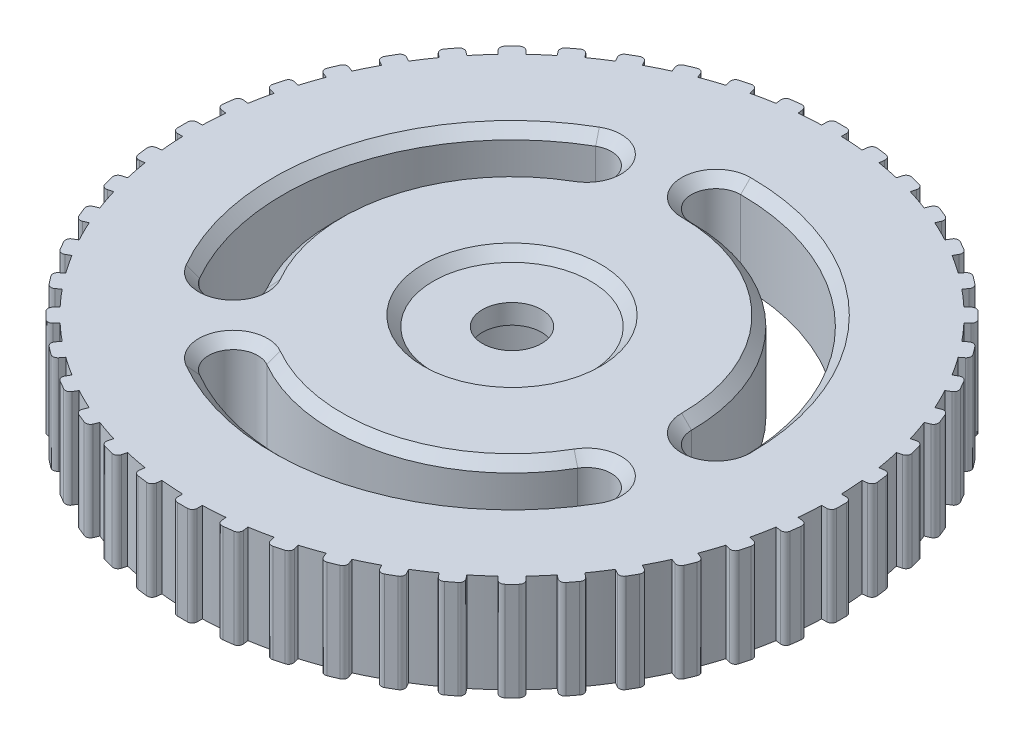
SolidWorks part; units mm, degrees
ref_plane "Front Plane" through (0, 0, 0) normal (0, 0, 1) x (1, 0, 0)
ref_plane "Top Plane" through (0, 0, 0) normal (0, 1, 0) x (1, 0, 0)
ref_plane "Right Plane" through (0, 0, 0) normal (1, 0, 0) x (0, 0, -1)
sketch "Sketch1" plane through (0, 0, 0) normal (0, 1, 0) x (1, 0, 0)
  line L0 (0, 65) -> (2, 65)
  line L1 (0, 65) -> (-2, 65)
  line L2 (-2, 65) -> (-2, 66)
  line L3 (2, 65) -> (2, 66)
  line L4 (-1, 67) -> (1, 67)
  line L5 (7.7538, 66.5573) -> (9.7367, 66.2963)
  line L6 (10.4671, 64.1829) -> (10.5976, 65.1743)
  line L7 (8.4842, 64.4439) -> (10.4671, 64.1829)
  line L8 (8.4842, 64.4439) -> (6.5013, 64.705)
  line L9 (6.5013, 64.705) -> (6.6318, 65.6964)
  line L10 (16.375, 64.9758) -> (18.3068, 64.4582)
  line L11 (18.7551, 62.2675) -> (19.0139, 63.2335)
  line L12 (16.8232, 62.7852) -> (18.7551, 62.2675)
  line L13 (16.8232, 62.7852) -> (14.8914, 63.3028)
  line L14 (14.8914, 63.3028) -> (15.1502, 64.2687)
  line L15 (24.7159, 62.2826) -> (26.5637, 61.5172)
  line L16 (26.7222, 59.2868) -> (27.1049, 60.2107)
  line L17 (24.8744, 60.0522) -> (26.7222, 59.2868)
  line L18 (24.8744, 60.0522) -> (23.0267, 60.8175)
  line L19 (23.0267, 60.8175) -> (23.4093, 61.7414)
  line L20 (32.634, 58.5237) -> (34.366, 57.5237)
  line L21 (34.2321, 55.2917) -> (34.7321, 56.1577)
  line L22 (32.5, 56.2917) -> (34.2321, 55.2917)
  line L23 (32.5, 56.2917) -> (30.7679, 57.2917)
  line L24 (30.7679, 57.2917) -> (31.2679, 58.1577)
  line L25 (39.9937, 53.7634) -> (41.5804, 52.5459)
  line L26 (41.1562, 50.3504) -> (41.765, 51.1438)
  line L27 (39.5695, 51.568) -> (41.1562, 50.3504)
  line L28 (39.5695, 51.568) -> (37.9828, 52.7855)
  line L29 (37.9828, 52.7855) -> (38.5915, 53.5788)
  line L30 (46.669, 48.0833) -> (48.0833, 46.669)
  line L31 (47.3762, 44.5477) -> (48.0833, 45.2548)
  line L32 (45.9619, 45.9619) -> (47.3762, 44.5477)
  line L33 (45.9619, 45.9619) -> (44.5477, 47.3762)
  line L34 (44.5477, 47.3762) -> (45.2548, 48.0833)
  line L35 (52.5459, 41.5804) -> (53.7634, 39.9937)
  line L36 (52.7855, 37.9828) -> (53.5788, 38.5915)
  line L37 (51.568, 39.5695) -> (52.7855, 37.9828)
  line L38 (51.568, 39.5695) -> (50.3504, 41.1562)
  line L39 (50.3504, 41.1562) -> (51.1438, 41.765)
  line L40 (57.5237, 34.366) -> (58.5237, 32.634)
  line L41 (57.2917, 30.7679) -> (58.1577, 31.2679)
  line L42 (56.2917, 32.5) -> (57.2917, 30.7679)
  line L43 (56.2917, 32.5) -> (55.2917, 34.2321)
  line L44 (55.2917, 34.2321) -> (56.1577, 34.7321)
  line L45 (61.5172, 26.5637) -> (62.2826, 24.7159)
  line L46 (60.8175, 23.0267) -> (61.7414, 23.4093)
  line L47 (60.0522, 24.8744) -> (60.8175, 23.0267)
  line L48 (60.0522, 24.8744) -> (59.2868, 26.7222)
  line L49 (59.2868, 26.7222) -> (60.2107, 27.1049)
  line L50 (64.4582, 18.3068) -> (64.9758, 16.375)
  line L51 (63.3028, 14.8914) -> (64.2687, 15.1502)
  line L52 (62.7852, 16.8232) -> (63.3028, 14.8914)
  line L53 (62.7852, 16.8232) -> (62.2675, 18.7551)
  line L54 (62.2675, 18.7551) -> (63.2335, 19.0139)
  line L55 (66.2963, 9.7367) -> (66.5573, 7.7538)
  line L56 (64.705, 6.5013) -> (65.6964, 6.6318)
  line L57 (64.4439, 8.4842) -> (64.705, 6.5013)
  line L58 (64.4439, 8.4842) -> (64.1829, 10.4671)
  line L59 (64.1829, 10.4671) -> (65.1743, 10.5976)
  line L60 (67, 1) -> (67, -1)
  line L61 (65, -2) -> (66, -2)
  line L62 (65, 0) -> (65, -2)
  line L63 (65, 0) -> (65, 2)
  line L64 (65, 2) -> (66, 2)
  line L65 (66.5573, -7.7538) -> (66.2963, -9.7367)
  line L66 (64.1829, -10.4671) -> (65.1743, -10.5976)
  line L67 (64.4439, -8.4842) -> (64.1829, -10.4671)
  line L68 (64.4439, -8.4842) -> (64.705, -6.5013)
  line L69 (64.705, -6.5013) -> (65.6964, -6.6318)
  line L70 (64.9758, -16.375) -> (64.4582, -18.3068)
  line L71 (62.2675, -18.7551) -> (63.2335, -19.0139)
  line L72 (62.7852, -16.8232) -> (62.2675, -18.7551)
  line L73 (62.7852, -16.8232) -> (63.3028, -14.8914)
  line L74 (63.3028, -14.8914) -> (64.2687, -15.1502)
  line L75 (62.2826, -24.7159) -> (61.5172, -26.5637)
  line L76 (59.2868, -26.7222) -> (60.2107, -27.1049)
  line L77 (60.0522, -24.8744) -> (59.2868, -26.7222)
  line L78 (60.0522, -24.8744) -> (60.8175, -23.0267)
  line L79 (60.8175, -23.0267) -> (61.7414, -23.4093)
  line L80 (58.5237, -32.634) -> (57.5237, -34.366)
  line L81 (55.2917, -34.2321) -> (56.1577, -34.7321)
  line L82 (56.2917, -32.5) -> (55.2917, -34.2321)
  line L83 (56.2917, -32.5) -> (57.2917, -30.7679)
  line L84 (57.2917, -30.7679) -> (58.1577, -31.2679)
  line L85 (53.7634, -39.9937) -> (52.5459, -41.5804)
  line L86 (50.3504, -41.1562) -> (51.1438, -41.765)
  line L87 (51.568, -39.5695) -> (50.3504, -41.1562)
  line L88 (51.568, -39.5695) -> (52.7855, -37.9828)
  line L89 (52.7855, -37.9828) -> (53.5788, -38.5915)
  line L90 (48.0833, -46.669) -> (46.669, -48.0833)
  line L91 (44.5477, -47.3762) -> (45.2548, -48.0833)
  line L92 (45.9619, -45.9619) -> (44.5477, -47.3762)
  line L93 (45.9619, -45.9619) -> (47.3762, -44.5477)
  line L94 (47.3762, -44.5477) -> (48.0833, -45.2548)
  line L95 (41.5804, -52.5459) -> (39.9937, -53.7634)
  line L96 (37.9828, -52.7855) -> (38.5915, -53.5788)
  line L97 (39.5695, -51.568) -> (37.9828, -52.7855)
  line L98 (39.5695, -51.568) -> (41.1562, -50.3504)
  line L99 (41.1562, -50.3504) -> (41.765, -51.1438)
  line L100 (34.366, -57.5237) -> (32.634, -58.5237)
  line L101 (30.7679, -57.2917) -> (31.2679, -58.1577)
  line L102 (32.5, -56.2917) -> (30.7679, -57.2917)
  line L103 (32.5, -56.2917) -> (34.2321, -55.2917)
  line L104 (34.2321, -55.2917) -> (34.7321, -56.1577)
  line L105 (26.5637, -61.5172) -> (24.7159, -62.2826)
  line L106 (23.0267, -60.8175) -> (23.4093, -61.7414)
  line L107 (24.8744, -60.0522) -> (23.0267, -60.8175)
  line L108 (24.8744, -60.0522) -> (26.7222, -59.2868)
  line L109 (26.7222, -59.2868) -> (27.1049, -60.2107)
  line L110 (18.3068, -64.4582) -> (16.375, -64.9758)
  line L111 (14.8914, -63.3028) -> (15.1502, -64.2687)
  line L112 (16.8232, -62.7852) -> (14.8914, -63.3028)
  line L113 (16.8232, -62.7852) -> (18.7551, -62.2675)
  line L114 (18.7551, -62.2675) -> (19.0139, -63.2335)
  line L115 (9.7367, -66.2963) -> (7.7538, -66.5573)
  line L116 (6.5013, -64.705) -> (6.6318, -65.6964)
  line L117 (8.4842, -64.4439) -> (6.5013, -64.705)
  line L118 (8.4842, -64.4439) -> (10.4671, -64.1829)
  line L119 (10.4671, -64.1829) -> (10.5976, -65.1743)
  line L120 (1, -67) -> (-1, -67)
  line L121 (-2, -65) -> (-2, -66)
  line L122 (0, -65) -> (-2, -65)
  line L123 (0, -65) -> (2, -65)
  line L124 (2, -65) -> (2, -66)
  line L125 (-7.7538, -66.5573) -> (-9.7367, -66.2963)
  line L126 (-10.4671, -64.1829) -> (-10.5976, -65.1743)
  line L127 (-8.4842, -64.4439) -> (-10.4671, -64.1829)
  line L128 (-8.4842, -64.4439) -> (-6.5013, -64.705)
  line L129 (-6.5013, -64.705) -> (-6.6318, -65.6964)
  line L130 (-16.375, -64.9758) -> (-18.3068, -64.4582)
  line L131 (-18.7551, -62.2675) -> (-19.0139, -63.2335)
  line L132 (-16.8232, -62.7852) -> (-18.7551, -62.2675)
  line L133 (-16.8232, -62.7852) -> (-14.8914, -63.3028)
  line L134 (-14.8914, -63.3028) -> (-15.1502, -64.2687)
  line L135 (-24.7159, -62.2826) -> (-26.5637, -61.5172)
  line L136 (-26.7222, -59.2868) -> (-27.1049, -60.2107)
  line L137 (-24.8744, -60.0522) -> (-26.7222, -59.2868)
  line L138 (-24.8744, -60.0522) -> (-23.0267, -60.8175)
  line L139 (-23.0267, -60.8175) -> (-23.4093, -61.7414)
  line L140 (-32.634, -58.5237) -> (-34.366, -57.5237)
  line L141 (-34.2321, -55.2917) -> (-34.7321, -56.1577)
  line L142 (-32.5, -56.2917) -> (-34.2321, -55.2917)
  line L143 (-32.5, -56.2917) -> (-30.7679, -57.2917)
  line L144 (-30.7679, -57.2917) -> (-31.2679, -58.1577)
  line L145 (-39.9937, -53.7634) -> (-41.5804, -52.5459)
  line L146 (-41.1562, -50.3504) -> (-41.765, -51.1438)
  line L147 (-39.5695, -51.568) -> (-41.1562, -50.3504)
  line L148 (-39.5695, -51.568) -> (-37.9828, -52.7855)
  line L149 (-37.9828, -52.7855) -> (-38.5915, -53.5788)
  line L150 (-46.669, -48.0833) -> (-48.0833, -46.669)
  line L151 (-47.3762, -44.5477) -> (-48.0833, -45.2548)
  line L152 (-45.9619, -45.9619) -> (-47.3762, -44.5477)
  line L153 (-45.9619, -45.9619) -> (-44.5477, -47.3762)
  line L154 (-44.5477, -47.3762) -> (-45.2548, -48.0833)
  line L155 (-52.5459, -41.5804) -> (-53.7634, -39.9937)
  line L156 (-52.7855, -37.9828) -> (-53.5788, -38.5915)
  line L157 (-51.568, -39.5695) -> (-52.7855, -37.9828)
  line L158 (-51.568, -39.5695) -> (-50.3504, -41.1562)
  line L159 (-50.3504, -41.1562) -> (-51.1438, -41.765)
  line L160 (-57.5237, -34.366) -> (-58.5237, -32.634)
  line L161 (-57.2917, -30.7679) -> (-58.1577, -31.2679)
  line L162 (-56.2917, -32.5) -> (-57.2917, -30.7679)
  line L163 (-56.2917, -32.5) -> (-55.2917, -34.2321)
  line L164 (-55.2917, -34.2321) -> (-56.1577, -34.7321)
  line L165 (-61.5172, -26.5637) -> (-62.2826, -24.7159)
  line L166 (-60.8175, -23.0267) -> (-61.7414, -23.4093)
  line L167 (-60.0522, -24.8744) -> (-60.8175, -23.0267)
  line L168 (-60.0522, -24.8744) -> (-59.2868, -26.7222)
  line L169 (-59.2868, -26.7222) -> (-60.2107, -27.1049)
  line L170 (-64.4582, -18.3068) -> (-64.9758, -16.375)
  line L171 (-63.3028, -14.8914) -> (-64.2687, -15.1502)
  line L172 (-62.7852, -16.8232) -> (-63.3028, -14.8914)
  line L173 (-62.7852, -16.8232) -> (-62.2675, -18.7551)
  line L174 (-62.2675, -18.7551) -> (-63.2335, -19.0139)
  line L175 (-66.2963, -9.7367) -> (-66.5573, -7.7538)
  line L176 (-64.705, -6.5013) -> (-65.6964, -6.6318)
  line L177 (-64.4439, -8.4842) -> (-64.705, -6.5013)
  line L178 (-64.4439, -8.4842) -> (-64.1829, -10.4671)
  line L179 (-64.1829, -10.4671) -> (-65.1743, -10.5976)
  line L180 (-67, -1) -> (-67, 1)
  line L181 (-65, 2) -> (-66, 2)
  line L182 (-65, 0) -> (-65, 2)
  line L183 (-65, 0) -> (-65, -2)
  line L184 (-65, -2) -> (-66, -2)
  line L185 (-66.5573, 7.7538) -> (-66.2963, 9.7367)
  line L186 (-64.1829, 10.4671) -> (-65.1743, 10.5976)
  line L187 (-64.4439, 8.4842) -> (-64.1829, 10.4671)
  line L188 (-64.4439, 8.4842) -> (-64.705, 6.5013)
  line L189 (-64.705, 6.5013) -> (-65.6964, 6.6318)
  line L190 (-64.9758, 16.375) -> (-64.4582, 18.3068)
  line L191 (-62.2675, 18.7551) -> (-63.2335, 19.0139)
  line L192 (-62.7852, 16.8232) -> (-62.2675, 18.7551)
  line L193 (-62.7852, 16.8232) -> (-63.3028, 14.8914)
  line L194 (-63.3028, 14.8914) -> (-64.2687, 15.1502)
  line L195 (-62.2826, 24.7159) -> (-61.5172, 26.5637)
  line L196 (-59.2868, 26.7222) -> (-60.2107, 27.1049)
  line L197 (-60.0522, 24.8744) -> (-59.2868, 26.7222)
  line L198 (-60.0522, 24.8744) -> (-60.8175, 23.0267)
  line L199 (-60.8175, 23.0267) -> (-61.7414, 23.4093)
  line L200 (-58.5237, 32.634) -> (-57.5237, 34.366)
  line L201 (-55.2917, 34.2321) -> (-56.1577, 34.7321)
  line L202 (-56.2917, 32.5) -> (-55.2917, 34.2321)
  line L203 (-56.2917, 32.5) -> (-57.2917, 30.7679)
  line L204 (-57.2917, 30.7679) -> (-58.1577, 31.2679)
  line L205 (-53.7634, 39.9937) -> (-52.5459, 41.5804)
  line L206 (-50.3504, 41.1562) -> (-51.1438, 41.765)
  line L207 (-51.568, 39.5695) -> (-50.3504, 41.1562)
  line L208 (-51.568, 39.5695) -> (-52.7855, 37.9828)
  line L209 (-52.7855, 37.9828) -> (-53.5788, 38.5915)
  line L210 (-48.0833, 46.669) -> (-46.669, 48.0833)
  line L211 (-44.5477, 47.3762) -> (-45.2548, 48.0833)
  line L212 (-45.9619, 45.9619) -> (-44.5477, 47.3762)
  line L213 (-45.9619, 45.9619) -> (-47.3762, 44.5477)
  line L214 (-47.3762, 44.5477) -> (-48.0833, 45.2548)
  line L215 (-41.5804, 52.5459) -> (-39.9937, 53.7634)
  line L216 (-37.9828, 52.7855) -> (-38.5915, 53.5788)
  line L217 (-39.5695, 51.568) -> (-37.9828, 52.7855)
  line L218 (-39.5695, 51.568) -> (-41.1562, 50.3504)
  line L219 (-41.1562, 50.3504) -> (-41.765, 51.1438)
  line L220 (-34.366, 57.5237) -> (-32.634, 58.5237)
  line L221 (-30.7679, 57.2917) -> (-31.2679, 58.1577)
  line L222 (-32.5, 56.2917) -> (-30.7679, 57.2917)
  line L223 (-32.5, 56.2917) -> (-34.2321, 55.2917)
  line L224 (-34.2321, 55.2917) -> (-34.7321, 56.1577)
  line L225 (-26.5637, 61.5172) -> (-24.7159, 62.2826)
  line L226 (-23.0267, 60.8175) -> (-23.4093, 61.7414)
  line L227 (-24.8744, 60.0522) -> (-23.0267, 60.8175)
  line L228 (-24.8744, 60.0522) -> (-26.7222, 59.2868)
  line L229 (-26.7222, 59.2868) -> (-27.1049, 60.2107)
  line L230 (-18.3068, 64.4582) -> (-16.375, 64.9758)
  line L231 (-14.8914, 63.3028) -> (-15.1502, 64.2687)
  line L232 (-16.8232, 62.7852) -> (-14.8914, 63.3028)
  line L233 (-16.8232, 62.7852) -> (-18.7551, 62.2675)
  line L234 (-18.7551, 62.2675) -> (-19.0139, 63.2335)
  line L235 (-9.7367, 66.2963) -> (-7.7538, 66.5573)
  line L236 (-6.5013, 64.705) -> (-6.6318, 65.6964)
  line L237 (-8.4842, 64.4439) -> (-6.5013, 64.705)
  line L238 (-8.4842, 64.4439) -> (-10.4671, 64.1829)
  line L239 (-10.4671, 64.1829) -> (-10.5976, 65.1743)
  circle A0 centre (0, 0) radius 18.5
  circle A1 centre (0, 0) radius 65
  arc A2 (-2, 66) -> (-1, 67) centre (-1, 66) cw
  arc A3 (1, 67) -> (2, 66) centre (1, 66) cw
  arc A4 (9.7367, 66.2963) -> (10.5976, 65.1743) centre (9.6062, 65.3048) cw
  arc A5 (6.6318, 65.6964) -> (7.7538, 66.5573) centre (7.6233, 65.5659) cw
  arc A6 (18.3068, 64.4582) -> (19.0139, 63.2335) centre (18.048, 63.4923) cw
  arc A7 (15.1502, 64.2687) -> (16.375, 64.9758) centre (16.1161, 64.0099) cw
  arc A8 (26.5637, 61.5172) -> (27.1049, 60.2107) centre (26.181, 60.5934) cw
  arc A9 (23.4093, 61.7414) -> (24.7159, 62.2826) centre (24.3332, 61.3587) cw
  arc A10 (34.366, 57.5237) -> (34.7321, 56.1577) centre (33.866, 56.6577) cw
  arc A11 (31.2679, 58.1577) -> (32.634, 58.5237) centre (32.134, 57.6577) cw
  arc A12 (41.5804, 52.5459) -> (41.765, 51.1438) centre (40.9716, 51.7526) cw
  arc A13 (38.5915, 53.5788) -> (39.9937, 53.7634) centre (39.3849, 52.9701) cw
  arc A14 (48.0833, 46.669) -> (48.0833, 45.2548) centre (47.3762, 45.9619) cw
  arc A15 (45.2548, 48.0833) -> (46.669, 48.0833) centre (45.9619, 47.3762) cw
  arc A16 (53.7634, 39.9937) -> (53.5788, 38.5915) centre (52.9701, 39.3849) cw
  arc A17 (51.1438, 41.765) -> (52.5459, 41.5804) centre (51.7526, 40.9716) cw
  arc A18 (58.5237, 32.634) -> (58.1577, 31.2679) centre (57.6577, 32.134) cw
  arc A19 (56.1577, 34.7321) -> (57.5237, 34.366) centre (56.6577, 33.866) cw
  arc A20 (62.2826, 24.7159) -> (61.7414, 23.4093) centre (61.3587, 24.3332) cw
  arc A21 (60.2107, 27.1049) -> (61.5172, 26.5637) centre (60.5934, 26.181) cw
  arc A22 (64.9758, 16.375) -> (64.2687, 15.1502) centre (64.0099, 16.1161) cw
  arc A23 (63.2335, 19.0139) -> (64.4582, 18.3068) centre (63.4923, 18.048) cw
  arc A24 (66.5573, 7.7538) -> (65.6964, 6.6318) centre (65.5659, 7.6233) cw
  arc A25 (65.1743, 10.5976) -> (66.2963, 9.7367) centre (65.3048, 9.6062) cw
  arc A26 (67, -1) -> (66, -2) centre (66, -1) cw
  arc A27 (66, 2) -> (67, 1) centre (66, 1) cw
  arc A28 (66.2963, -9.7367) -> (65.1743, -10.5976) centre (65.3048, -9.6062) cw
  arc A29 (65.6964, -6.6318) -> (66.5573, -7.7538) centre (65.5659, -7.6233) cw
  arc A30 (64.4582, -18.3068) -> (63.2335, -19.0139) centre (63.4923, -18.048) cw
  arc A31 (64.2687, -15.1502) -> (64.9758, -16.375) centre (64.0099, -16.1161) cw
  arc A32 (61.5172, -26.5637) -> (60.2107, -27.1049) centre (60.5934, -26.181) cw
  arc A33 (61.7414, -23.4093) -> (62.2826, -24.7159) centre (61.3587, -24.3332) cw
  arc A34 (57.5237, -34.366) -> (56.1577, -34.7321) centre (56.6577, -33.866) cw
  arc A35 (58.1577, -31.2679) -> (58.5237, -32.634) centre (57.6577, -32.134) cw
  arc A36 (52.5459, -41.5804) -> (51.1438, -41.765) centre (51.7526, -40.9716) cw
  arc A37 (53.5788, -38.5915) -> (53.7634, -39.9937) centre (52.9701, -39.3849) cw
  arc A38 (46.669, -48.0833) -> (45.2548, -48.0833) centre (45.9619, -47.3762) cw
  arc A39 (48.0833, -45.2548) -> (48.0833, -46.669) centre (47.3762, -45.9619) cw
  arc A40 (39.9937, -53.7634) -> (38.5915, -53.5788) centre (39.3849, -52.9701) cw
  arc A41 (41.765, -51.1438) -> (41.5804, -52.5459) centre (40.9716, -51.7526) cw
  arc A42 (32.634, -58.5237) -> (31.2679, -58.1577) centre (32.134, -57.6577) cw
  arc A43 (34.7321, -56.1577) -> (34.366, -57.5237) centre (33.866, -56.6577) cw
  arc A44 (24.7159, -62.2826) -> (23.4093, -61.7414) centre (24.3332, -61.3587) cw
  arc A45 (27.1049, -60.2107) -> (26.5637, -61.5172) centre (26.181, -60.5934) cw
  arc A46 (16.375, -64.9758) -> (15.1502, -64.2687) centre (16.1161, -64.0099) cw
  arc A47 (19.0139, -63.2335) -> (18.3068, -64.4582) centre (18.048, -63.4923) cw
  arc A48 (7.7538, -66.5573) -> (6.6318, -65.6964) centre (7.6233, -65.5659) cw
  arc A49 (10.5976, -65.1743) -> (9.7367, -66.2963) centre (9.6062, -65.3048) cw
  arc A50 (-1, -67) -> (-2, -66) centre (-1, -66) cw
  arc A51 (2, -66) -> (1, -67) centre (1, -66) cw
  arc A52 (-9.7367, -66.2963) -> (-10.5976, -65.1743) centre (-9.6062, -65.3048) cw
  arc A53 (-6.6318, -65.6964) -> (-7.7538, -66.5573) centre (-7.6233, -65.5659) cw
  arc A54 (-18.3068, -64.4582) -> (-19.0139, -63.2335) centre (-18.048, -63.4923) cw
  arc A55 (-15.1502, -64.2687) -> (-16.375, -64.9758) centre (-16.1161, -64.0099) cw
  arc A56 (-26.5637, -61.5172) -> (-27.1049, -60.2107) centre (-26.181, -60.5934) cw
  arc A57 (-23.4093, -61.7414) -> (-24.7159, -62.2826) centre (-24.3332, -61.3587) cw
  arc A58 (-34.366, -57.5237) -> (-34.7321, -56.1577) centre (-33.866, -56.6577) cw
  arc A59 (-31.2679, -58.1577) -> (-32.634, -58.5237) centre (-32.134, -57.6577) cw
  arc A60 (-41.5804, -52.5459) -> (-41.765, -51.1438) centre (-40.9716, -51.7526) cw
  arc A61 (-38.5915, -53.5788) -> (-39.9937, -53.7634) centre (-39.3849, -52.9701) cw
  arc A62 (-48.0833, -46.669) -> (-48.0833, -45.2548) centre (-47.3762, -45.9619) cw
  arc A63 (-45.2548, -48.0833) -> (-46.669, -48.0833) centre (-45.9619, -47.3762) cw
  arc A64 (-53.7634, -39.9937) -> (-53.5788, -38.5915) centre (-52.9701, -39.3849) cw
  arc A65 (-51.1438, -41.765) -> (-52.5459, -41.5804) centre (-51.7526, -40.9716) cw
  arc A66 (-58.5237, -32.634) -> (-58.1577, -31.2679) centre (-57.6577, -32.134) cw
  arc A67 (-56.1577, -34.7321) -> (-57.5237, -34.366) centre (-56.6577, -33.866) cw
  arc A68 (-62.2826, -24.7159) -> (-61.7414, -23.4093) centre (-61.3587, -24.3332) cw
  arc A69 (-60.2107, -27.1049) -> (-61.5172, -26.5637) centre (-60.5934, -26.181) cw
  arc A70 (-64.9758, -16.375) -> (-64.2687, -15.1502) centre (-64.0099, -16.1161) cw
  arc A71 (-63.2335, -19.0139) -> (-64.4582, -18.3068) centre (-63.4923, -18.048) cw
  arc A72 (-66.5573, -7.7538) -> (-65.6964, -6.6318) centre (-65.5659, -7.6233) cw
  arc A73 (-65.1743, -10.5976) -> (-66.2963, -9.7367) centre (-65.3048, -9.6062) cw
  arc A74 (-67, 1) -> (-66, 2) centre (-66, 1) cw
  arc A75 (-66, -2) -> (-67, -1) centre (-66, -1) cw
  arc A76 (-66.2963, 9.7367) -> (-65.1743, 10.5976) centre (-65.3048, 9.6062) cw
  arc A77 (-65.6964, 6.6318) -> (-66.5573, 7.7538) centre (-65.5659, 7.6233) cw
  arc A78 (-64.4582, 18.3068) -> (-63.2335, 19.0139) centre (-63.4923, 18.048) cw
  arc A79 (-64.2687, 15.1502) -> (-64.9758, 16.375) centre (-64.0099, 16.1161) cw
  arc A80 (-61.5172, 26.5637) -> (-60.2107, 27.1049) centre (-60.5934, 26.181) cw
  arc A81 (-61.7414, 23.4093) -> (-62.2826, 24.7159) centre (-61.3587, 24.3332) cw
  arc A82 (-57.5237, 34.366) -> (-56.1577, 34.7321) centre (-56.6577, 33.866) cw
  arc A83 (-58.1577, 31.2679) -> (-58.5237, 32.634) centre (-57.6577, 32.134) cw
  arc A84 (-52.5459, 41.5804) -> (-51.1438, 41.765) centre (-51.7526, 40.9716) cw
  arc A85 (-53.5788, 38.5915) -> (-53.7634, 39.9937) centre (-52.9701, 39.3849) cw
  arc A86 (-46.669, 48.0833) -> (-45.2548, 48.0833) centre (-45.9619, 47.3762) cw
  arc A87 (-48.0833, 45.2548) -> (-48.0833, 46.669) centre (-47.3762, 45.9619) cw
  arc A88 (-39.9937, 53.7634) -> (-38.5915, 53.5788) centre (-39.3849, 52.9701) cw
  arc A89 (-41.765, 51.1438) -> (-41.5804, 52.5459) centre (-40.9716, 51.7526) cw
  arc A90 (-32.634, 58.5237) -> (-31.2679, 58.1577) centre (-32.134, 57.6577) cw
  arc A91 (-34.7321, 56.1577) -> (-34.366, 57.5237) centre (-33.866, 56.6577) cw
  arc A92 (-24.7159, 62.2826) -> (-23.4093, 61.7414) centre (-24.3332, 61.3587) cw
  arc A93 (-27.1049, 60.2107) -> (-26.5637, 61.5172) centre (-26.181, 60.5934) cw
  arc A94 (-16.375, 64.9758) -> (-15.1502, 64.2687) centre (-16.1161, 64.0099) cw
  arc A95 (-19.0139, 63.2335) -> (-18.3068, 64.4582) centre (-18.048, 63.4923) cw
  arc A96 (-7.7538, 66.5573) -> (-6.6318, 65.6964) centre (-7.6233, 65.5659) cw
  arc A97 (-10.5976, 65.1743) -> (-9.7367, 66.2963) centre (-9.6062, 65.3048) cw
  point P11 (-2, 67)
  point P14 (2, 67)
  point P441 (0, 0)
  dimension "D1" = 130
  dimension "D2" = 37
  dimension "D7" = 1
  dimension "D8" = 1
  dimension "D3" = 2
  dimension "D4" = 2
  dimension "D5" = 2
  dimension "D6" = 2
  dimension "D9" = 48
extrude "Boss-Extrude1" add sketch "Sketch1" along normal blind 20 contours A1 A0 | A59 L144 L143 L142 L141 A58 L140 | A61 L149 L148 L147 L146 A60 L145 | A57 L139 L138 L137 L136 A56 L135 | A55 L134 L133 L132 L131 A54 L130 | A53 L129 L128 L127 L126 A52 L125 | A51 L124 L123 L122 L121 A50 L120 | A49 L119 L118 L117 L116 A48 L115 | A45 L109 L108 L107 L106 A44 L105 | A43 L104 L103 L102 L101 A42 L100 | A41 L99 L98 L97 L96 A40 L95 | A39 L94 L93 L92 L91 A38 L90 | A37 L89 L88 L87 L86 A36 L85 | A35 L84 L83 L82 L81 A34 L80 | A33 L79 L78 L77 L76 A32 L75 | A31 L74 L73 L72 L71 A30 L70 | A29 L69 L68 L67 L66 A28 L65 | A27 L64 L63 L62 L61 A26 L60 | A25 L59 L58 L57 L56 A24 L55 | A21 L49 L48 L47 L46 A20 L45 | A19 L44 L43 L42 L41 A18 L40 | A17 L39 L38 L37 L36 A16 L35 | A15 L34 L33 L32 L31 A14 L30 | A13 L29 L28 L27 L26 A12 L25 | A11 L24 L23 L22 L21 A10 L20 | A9 L19 L18 L17 L16 A8 L15 | A7 L14 L13 L12 L11 A6 L10 | A5 L9 L8 L7 L6 A4 L5 | A3 L4 A2 L2 L1 L0 L3 | A97 L239 L238 L237 L236 A96 L235 | A95 L234 L233 L232 L231 A94 L230 | A89 L219 L218 L217 L216 A88 L215 | A91 L224 L223 L222 L221 A90 L220 | A93 L229 L228 L227 L226 A92 L225 | A85 L209 L208 L207 L206 A84 L205 | A87 L214 L213 L212 L211 A86 L210 | A83 L204 L203 L202 L201 A82 L200 | A77 L189 L188 L187 L186 A76 L185 | A75 L184 L183 L182 L181 A74 L180 | A73 L179 L178 L177 L176 A72 L175 | A71 L174 L173 L172 L171 A70 L170 | A69 L169 L168 L167 L166 A68 L165 | A67 L164 L163 L162 L161 A66 L160 | A65 L159 L158 L157 L156 A64 L155 | A63 L154 L153 L152 L151 A62 L150 | L112 L111 A46 L110 A47 L114 L113 | L52 L51 A22 L50 A23 L54 L53 | L195 A80 L196 L197 L198 L199 A81 | L193 L194 A79 L190 A78 L191 L192 | L177 L176 A72 L175 A73 L179 L178 | L172 L171 A70 L170 A71 L174 L173 region at (0, 0, -65.956) region at (8.609, 0, -65.3917) region at (17.0707, 0, -63.7086) region at (25.2403, 0, -60.9354) region at (32.978, 0, -57.1195) region at (40.1515, 0, -52.3264) region at (46.6379, 0, -46.6379) region at (52.3264, 0, -40.1515) region at (57.1195, 0, -32.978) region at (60.9354, 0, -25.2403) region at (65.3917, 0, -8.609) region at (65.956, 0, 0) region at (65.3917, 0, 8.609) region at (63.7086, 0, 17.0707) region at (60.9354, 0, 25.2403) region at (57.1195, 0, 32.978) region at (52.3264, 0, 40.1515) region at (46.6379, 0, 46.6379) region at (40.1515, 0, 52.3264) region at (32.978, 0, 57.1195) region at (25.2403, 0, 60.9354) region at (8.609, 0, 65.3917) region at (0, 0, 65.956) region at (-8.609, 0, 65.3917) region at (-17.0707, 0, 63.7086) region at (-25.2403, 0, 60.9354) region at (-32.978, 0, 57.1195) region at (-40.1515, 0, 52.3264) region at (-46.6379, 0, 46.6379) region at (-52.3264, 0, 40.1515) region at (-57.1195, 0, 32.978) region at (-60.9354, 0, 25.2403) region at (-63.7086, 0, 17.0707) region at (-65.3917, 0, 8.609) region at (-65.956, 0, 0) region at (-65.3917, 0, -8.609) region at (-57.1195, 0, -32.978) region at (-52.3264, 0, -40.1515) region at (-46.6379, 0, -46.6379) region at (-40.1515, 0, -52.3264) region at (-32.978, 0, -57.1195) region at (-25.2403, 0, -60.9354) region at (-17.0707, 0, -63.7086) region at (-8.609, 0, -65.3917) region at (4.131, 0, -63.0263)
sketch "Sketch2" plane through (0, 20, 0) normal (0, 1, 0) x (1, 0, 0)
  line L0 (6.5013, 64.705) -> (6.2538, 62.8251)
  line L1 (-2, 65) -> (2, 65)
  line L2 (-2, 65) -> (-2, 63.1039)
  line L3 (-2, 63.1039) -> (2, 63.1039)
  line L4 (2, 65) -> (2, 63.1039)
  line L5 (6.5013, 64.705) -> (10.4671, 64.1829)
  line L6 (10.4671, 64.1829) -> (10.2196, 62.303)
  line L7 (6.2538, 62.8251) -> (10.2196, 62.303)
  line L8 (14.8914, 63.3028) -> (14.4006, 61.4713)
  line L9 (14.8914, 63.3028) -> (18.7551, 62.2675)
  line L10 (18.7551, 62.2675) -> (18.2643, 60.4361)
  line L11 (14.4006, 61.4713) -> (18.2643, 60.4361)
  line L12 (23.0267, 60.8175) -> (22.3011, 59.0658)
  line L13 (23.0267, 60.8175) -> (26.7222, 59.2868)
  line L14 (26.7222, 59.2868) -> (25.9966, 57.535)
  line L15 (22.3011, 59.0658) -> (25.9966, 57.535)
  line L16 (30.7679, 57.2917) -> (29.8199, 55.6496)
  line L17 (30.7679, 57.2917) -> (34.2321, 55.2917)
  line L18 (34.2321, 55.2917) -> (33.284, 53.6496)
  line L19 (29.8199, 55.6496) -> (33.284, 53.6496)
  line L20 (37.9828, 52.7855) -> (36.8285, 51.2812)
  line L21 (37.9828, 52.7855) -> (41.1562, 50.3504)
  line L22 (41.1562, 50.3504) -> (40.0019, 48.8462)
  line L23 (36.8285, 51.2812) -> (40.0019, 48.8462)
  line L24 (44.5477, 47.3762) -> (43.207, 46.0354)
  line L25 (44.5477, 47.3762) -> (47.3762, 44.5477)
  line L26 (47.3762, 44.5477) -> (46.0354, 43.207)
  line L27 (43.207, 46.0354) -> (46.0354, 43.207)
  line L28 (50.3504, 41.1562) -> (48.8462, 40.0019)
  line L29 (50.3504, 41.1562) -> (52.7855, 37.9828)
  line L30 (52.7855, 37.9828) -> (51.2812, 36.8285)
  line L31 (48.8462, 40.0019) -> (51.2812, 36.8285)
  line L32 (55.2917, 34.2321) -> (53.6496, 33.284)
  line L33 (55.2917, 34.2321) -> (57.2917, 30.7679)
  line L34 (57.2917, 30.7679) -> (55.6496, 29.8199)
  line L35 (53.6496, 33.284) -> (55.6496, 29.8199)
  line L36 (59.2868, 26.7222) -> (57.535, 25.9966)
  line L37 (59.2868, 26.7222) -> (60.8175, 23.0267)
  line L38 (60.8175, 23.0267) -> (59.0658, 22.3011)
  line L39 (57.535, 25.9966) -> (59.0658, 22.3011)
  line L40 (62.2675, 18.7551) -> (60.4361, 18.2643)
  line L41 (62.2675, 18.7551) -> (63.3028, 14.8914)
  line L42 (63.3028, 14.8914) -> (61.4713, 14.4006)
  line L43 (60.4361, 18.2643) -> (61.4713, 14.4006)
  line L44 (64.1829, 10.4671) -> (62.303, 10.2196)
  line L45 (64.1829, 10.4671) -> (64.705, 6.5013)
  line L46 (64.705, 6.5013) -> (62.8251, 6.2538)
  line L47 (62.303, 10.2196) -> (62.8251, 6.2538)
  line L48 (65, 2) -> (63.1039, 2)
  line L49 (65, 2) -> (65, -2)
  line L50 (65, -2) -> (63.1039, -2)
  line L51 (63.1039, 2) -> (63.1039, -2)
  line L52 (64.705, -6.5013) -> (62.8251, -6.2538)
  line L53 (64.705, -6.5013) -> (64.1829, -10.4671)
  line L54 (64.1829, -10.4671) -> (62.303, -10.2196)
  line L55 (62.8251, -6.2538) -> (62.303, -10.2196)
  line L56 (63.3028, -14.8914) -> (61.4713, -14.4006)
  line L57 (63.3028, -14.8914) -> (62.2675, -18.7551)
  line L58 (62.2675, -18.7551) -> (60.4361, -18.2643)
  line L59 (61.4713, -14.4006) -> (60.4361, -18.2643)
  line L60 (60.8175, -23.0267) -> (59.0658, -22.3011)
  line L61 (60.8175, -23.0267) -> (59.2868, -26.7222)
  line L62 (59.2868, -26.7222) -> (57.535, -25.9966)
  line L63 (59.0658, -22.3011) -> (57.535, -25.9966)
  line L64 (57.2917, -30.7679) -> (55.6496, -29.8199)
  line L65 (57.2917, -30.7679) -> (55.2917, -34.2321)
  line L66 (55.2917, -34.2321) -> (53.6496, -33.284)
  line L67 (55.6496, -29.8199) -> (53.6496, -33.284)
  line L68 (52.7855, -37.9828) -> (51.2812, -36.8285)
  line L69 (52.7855, -37.9828) -> (50.3504, -41.1562)
  line L70 (50.3504, -41.1562) -> (48.8462, -40.0019)
  line L71 (51.2812, -36.8285) -> (48.8462, -40.0019)
  line L72 (47.3762, -44.5477) -> (46.0354, -43.207)
  line L73 (47.3762, -44.5477) -> (44.5477, -47.3762)
  line L74 (44.5477, -47.3762) -> (43.207, -46.0354)
  line L75 (46.0354, -43.207) -> (43.207, -46.0354)
  line L76 (41.1562, -50.3504) -> (40.0019, -48.8462)
  line L77 (41.1562, -50.3504) -> (37.9828, -52.7855)
  line L78 (37.9828, -52.7855) -> (36.8285, -51.2812)
  line L79 (40.0019, -48.8462) -> (36.8285, -51.2812)
  line L80 (34.2321, -55.2917) -> (33.284, -53.6496)
  line L81 (34.2321, -55.2917) -> (30.7679, -57.2917)
  line L82 (30.7679, -57.2917) -> (29.8199, -55.6496)
  line L83 (33.284, -53.6496) -> (29.8199, -55.6496)
  line L84 (26.7222, -59.2868) -> (25.9966, -57.535)
  line L85 (26.7222, -59.2868) -> (23.0267, -60.8175)
  line L86 (23.0267, -60.8175) -> (22.3011, -59.0658)
  line L87 (25.9966, -57.535) -> (22.3011, -59.0658)
  line L88 (18.7551, -62.2675) -> (18.2643, -60.4361)
  line L89 (18.7551, -62.2675) -> (14.8914, -63.3028)
  line L90 (14.8914, -63.3028) -> (14.4006, -61.4713)
  line L91 (18.2643, -60.4361) -> (14.4006, -61.4713)
  line L92 (10.4671, -64.1829) -> (10.2196, -62.303)
  line L93 (10.4671, -64.1829) -> (6.5013, -64.705)
  line L94 (6.5013, -64.705) -> (6.2538, -62.8251)
  line L95 (10.2196, -62.303) -> (6.2538, -62.8251)
  line L96 (2, -65) -> (2, -63.1039)
  line L97 (2, -65) -> (-2, -65)
  line L98 (-2, -65) -> (-2, -63.1039)
  line L99 (2, -63.1039) -> (-2, -63.1039)
  line L100 (-6.5013, -64.705) -> (-6.2538, -62.8251)
  line L101 (-6.5013, -64.705) -> (-10.4671, -64.1829)
  line L102 (-10.4671, -64.1829) -> (-10.2196, -62.303)
  line L103 (-6.2538, -62.8251) -> (-10.2196, -62.303)
  line L104 (-14.8914, -63.3028) -> (-14.4006, -61.4713)
  line L105 (-14.8914, -63.3028) -> (-18.7551, -62.2675)
  line L106 (-18.7551, -62.2675) -> (-18.2643, -60.4361)
  line L107 (-14.4006, -61.4713) -> (-18.2643, -60.4361)
  line L108 (-23.0267, -60.8175) -> (-22.3011, -59.0658)
  line L109 (-23.0267, -60.8175) -> (-26.7222, -59.2868)
  line L110 (-26.7222, -59.2868) -> (-25.9966, -57.535)
  line L111 (-22.3011, -59.0658) -> (-25.9966, -57.535)
  line L112 (-30.7679, -57.2917) -> (-29.8199, -55.6496)
  line L113 (-30.7679, -57.2917) -> (-34.2321, -55.2917)
  line L114 (-34.2321, -55.2917) -> (-33.284, -53.6496)
  line L115 (-29.8199, -55.6496) -> (-33.284, -53.6496)
  line L116 (-37.9828, -52.7855) -> (-36.8285, -51.2812)
  line L117 (-37.9828, -52.7855) -> (-41.1562, -50.3504)
  line L118 (-41.1562, -50.3504) -> (-40.0019, -48.8462)
  line L119 (-36.8285, -51.2812) -> (-40.0019, -48.8462)
  line L120 (-44.5477, -47.3762) -> (-43.207, -46.0354)
  line L121 (-44.5477, -47.3762) -> (-47.3762, -44.5477)
  line L122 (-47.3762, -44.5477) -> (-46.0354, -43.207)
  line L123 (-43.207, -46.0354) -> (-46.0354, -43.207)
  line L124 (-50.3504, -41.1562) -> (-48.8462, -40.0019)
  line L125 (-50.3504, -41.1562) -> (-52.7855, -37.9828)
  line L126 (-52.7855, -37.9828) -> (-51.2812, -36.8285)
  line L127 (-48.8462, -40.0019) -> (-51.2812, -36.8285)
  line L128 (-55.2917, -34.2321) -> (-53.6496, -33.284)
  line L129 (-55.2917, -34.2321) -> (-57.2917, -30.7679)
  line L130 (-57.2917, -30.7679) -> (-55.6496, -29.8199)
  line L131 (-53.6496, -33.284) -> (-55.6496, -29.8199)
  line L132 (-59.2868, -26.7222) -> (-57.535, -25.9966)
  line L133 (-59.2868, -26.7222) -> (-60.8175, -23.0267)
  line L134 (-60.8175, -23.0267) -> (-59.0658, -22.3011)
  line L135 (-57.535, -25.9966) -> (-59.0658, -22.3011)
  line L136 (-62.2675, -18.7551) -> (-60.4361, -18.2643)
  line L137 (-62.2675, -18.7551) -> (-63.3028, -14.8914)
  line L138 (-63.3028, -14.8914) -> (-61.4713, -14.4006)
  line L139 (-60.4361, -18.2643) -> (-61.4713, -14.4006)
  line L140 (-64.1829, -10.4671) -> (-62.303, -10.2196)
  line L141 (-64.1829, -10.4671) -> (-64.705, -6.5013)
  line L142 (-64.705, -6.5013) -> (-62.8251, -6.2538)
  line L143 (-62.303, -10.2196) -> (-62.8251, -6.2538)
  line L144 (-65, -2) -> (-63.1039, -2)
  line L145 (-65, -2) -> (-65, 2)
  line L146 (-65, 2) -> (-63.1039, 2)
  line L147 (-63.1039, -2) -> (-63.1039, 2)
  line L148 (-64.705, 6.5013) -> (-62.8251, 6.2538)
  line L149 (-64.705, 6.5013) -> (-64.1829, 10.4671)
  line L150 (-64.1829, 10.4671) -> (-62.303, 10.2196)
  line L151 (-62.8251, 6.2538) -> (-62.303, 10.2196)
  line L152 (-63.3028, 14.8914) -> (-61.4713, 14.4006)
  line L153 (-63.3028, 14.8914) -> (-62.2675, 18.7551)
  line L154 (-62.2675, 18.7551) -> (-60.4361, 18.2643)
  line L155 (-61.4713, 14.4006) -> (-60.4361, 18.2643)
  line L156 (-60.8175, 23.0267) -> (-59.0658, 22.3011)
  line L157 (-60.8175, 23.0267) -> (-59.2868, 26.7222)
  line L158 (-59.2868, 26.7222) -> (-57.535, 25.9966)
  line L159 (-59.0658, 22.3011) -> (-57.535, 25.9966)
  line L160 (-57.2917, 30.7679) -> (-55.6496, 29.8199)
  line L161 (-57.2917, 30.7679) -> (-55.2917, 34.2321)
  line L162 (-55.2917, 34.2321) -> (-53.6496, 33.284)
  line L163 (-55.6496, 29.8199) -> (-53.6496, 33.284)
  line L164 (-52.7855, 37.9828) -> (-51.2812, 36.8285)
  line L165 (-52.7855, 37.9828) -> (-50.3504, 41.1562)
  line L166 (-50.3504, 41.1562) -> (-48.8462, 40.0019)
  line L167 (-51.2812, 36.8285) -> (-48.8462, 40.0019)
  line L168 (-47.3762, 44.5477) -> (-46.0354, 43.207)
  line L169 (-47.3762, 44.5477) -> (-44.5477, 47.3762)
  line L170 (-44.5477, 47.3762) -> (-43.207, 46.0354)
  line L171 (-46.0354, 43.207) -> (-43.207, 46.0354)
  line L172 (-41.1562, 50.3504) -> (-40.0019, 48.8462)
  line L173 (-41.1562, 50.3504) -> (-37.9828, 52.7855)
  line L174 (-37.9828, 52.7855) -> (-36.8285, 51.2812)
  line L175 (-40.0019, 48.8462) -> (-36.8285, 51.2812)
  line L176 (-34.2321, 55.2917) -> (-33.284, 53.6496)
  line L177 (-34.2321, 55.2917) -> (-30.7679, 57.2917)
  line L178 (-30.7679, 57.2917) -> (-29.8199, 55.6496)
  line L179 (-33.284, 53.6496) -> (-29.8199, 55.6496)
  line L180 (-26.7222, 59.2868) -> (-25.9966, 57.535)
  line L181 (-26.7222, 59.2868) -> (-23.0267, 60.8175)
  line L182 (-23.0267, 60.8175) -> (-22.3011, 59.0658)
  line L183 (-25.9966, 57.535) -> (-22.3011, 59.0658)
  line L184 (-18.7551, 62.2675) -> (-18.2643, 60.4361)
  line L185 (-18.7551, 62.2675) -> (-14.8914, 63.3028)
  line L186 (-14.8914, 63.3028) -> (-14.4006, 61.4713)
  line L187 (-18.2643, 60.4361) -> (-14.4006, 61.4713)
  line L188 (-10.4671, 64.1829) -> (-10.2196, 62.303)
  line L189 (-10.4671, 64.1829) -> (-6.5013, 64.705)
  line L190 (-6.5013, 64.705) -> (-6.2538, 62.8251)
  line L191 (-10.2196, 62.303) -> (-6.2538, 62.8251)
  point P196 (0, 0)
  dimension "D1" = 4
  dimension "D2" = 48
extrude "Boss-Extrude2" add sketch "Sketch2" against normal blind 20
sketch "Sketch3" plane through (0, 0, 0) normal (0, -1, 0) x (1, 0, 0)
  circle A0 centre (0, 0) radius 18.5
extrude "Boss-Extrude3" add sketch "Sketch3" against normal up to surface (20 mm away) up to face at (0, 20, 0)
sketch "Sketch4" plane through (0, 0, 0) normal (0, -1, 0) x (1, 0, 0)
  circle A0 centre (0, 0) radius 17
  dimension "D1" = 34
extrude "Cut-Extrude1" cut sketch "Sketch4" against normal blind 14
chamfer "Chamfer1" distance 6 angle 45 1 edges at (0, 14, -17)
sketch "Sketch5" plane through (0, 14, 0) normal (0, -1, 0) x (1, 0, 0)
  circle A0 centre (0, 0) radius 6
  dimension "D1" = 12
extrude "Cut-Extrude2" cut sketch "Sketch5" against normal blind 14
sketch "Sketch6" plane through (0, 20, 0) normal (0, 1, 0) x (1, 0, 0)
  circle A0 centre (0, 0) radius 12
  dimension "D1" = 24
extrude "Cut-Extrude3" cut sketch "Sketch6" against normal blind 2
chamfer "Chamfer2" distance 6 angle 45 1 edges at (0, 20, 12)
sketch "Sketch8" plane through (0, 20, 0) normal (0, 1, 0) x (1, 0, 0)
  line L0 (0, 18) -> (0, 65)
  circle A0 centre (0, 0) radius 65
  circle A1 centre (0, 0) radius 18 construction
  arc A2 (0, 41.5) -> (41.5, 0) centre (0, 0) cw
  arc A3 (0, 36.5) -> (36.5, 0) centre (0, 0) cw
  arc A4 (0, 46.5) -> (46.5, 0) centre (0, 0) cw
  arc A5 (0, 36.5) -> (0, 46.5) centre (0, 41.5) cw
  arc A6 (36.5, 0) -> (46.5, 0) centre (41.5, 0) ccw
  arc A7 (-18.25, -31.6099) -> (-23.25, -40.2702) centre (-20.75, -35.9401) ccw
  arc A8 (40.2702, -23.25) -> (-23.25, -40.2702) centre (0, 0) cw
  arc A9 (31.6099, -18.25) -> (40.2702, -23.25) centre (35.9401, -20.75) cw
  arc A10 (31.6099, -18.25) -> (-18.25, -31.6099) centre (0, 0) cw
  arc A11 (-18.25, 31.6099) -> (-23.25, 40.2702) centre (-20.75, 35.9401) ccw
  arc A12 (-40.2702, -23.25) -> (-23.25, 40.2702) centre (0, 0) cw
  arc A13 (-31.6099, -18.25) -> (-40.2702, -23.25) centre (-35.9401, -20.75) cw
  arc A14 (-31.6099, -18.25) -> (-18.25, 31.6099) centre (0, 0) cw
  point P32 (0, 0)
  dimension "D1" = 5
  dimension "D2" = 5
  dimension "D3" = 3
extrude "Cut-Extrude4" cut sketch "Sketch8" against normal blind 20 contours A13 A14 A11 A12 | A9 A10 A7 A8 | A3 A6 A4 L0 | A5 L0 region at (-2.1221, 20, -41.5) region at (27.3971, 20, -24.9186) region at (9.4471, 20, 35.2572) region at (-35.2572, 20, -9.4471)
chamfer "Chamfer3" distance 2 angle 45 24 edges at (12.0351, 0, 44.9156) (38.4401, 0, 16.4199) (-25.0801, 0, 33.4401) (9.4469, 0, 35.2563) (-35.2563, 0, -9.4469) (-33.4401, 0, 25.0801) (-16.4199, 0, -38.4401) (-44.9156, 0, -12.0351) (25.8094, 0, -25.8094) (-5, 0, -41.5) (41.5, 0, 5) (32.8805, 0, -32.8805) (-25.0801, 20, 33.4401) (9.4469, 20, 35.2563) (12.0351, 20, 44.9156) (38.4401, 20, 16.4199) (-33.4401, 20, 25.0801) (-35.2563, 20, -9.4469) (-44.9156, 20, -12.0351) (-16.4199, 20, -38.4401) (25.8094, 20, -25.8094) (-5, 20, -41.5) (41.5, 20, 5) (32.8805, 20, -32.8805)
